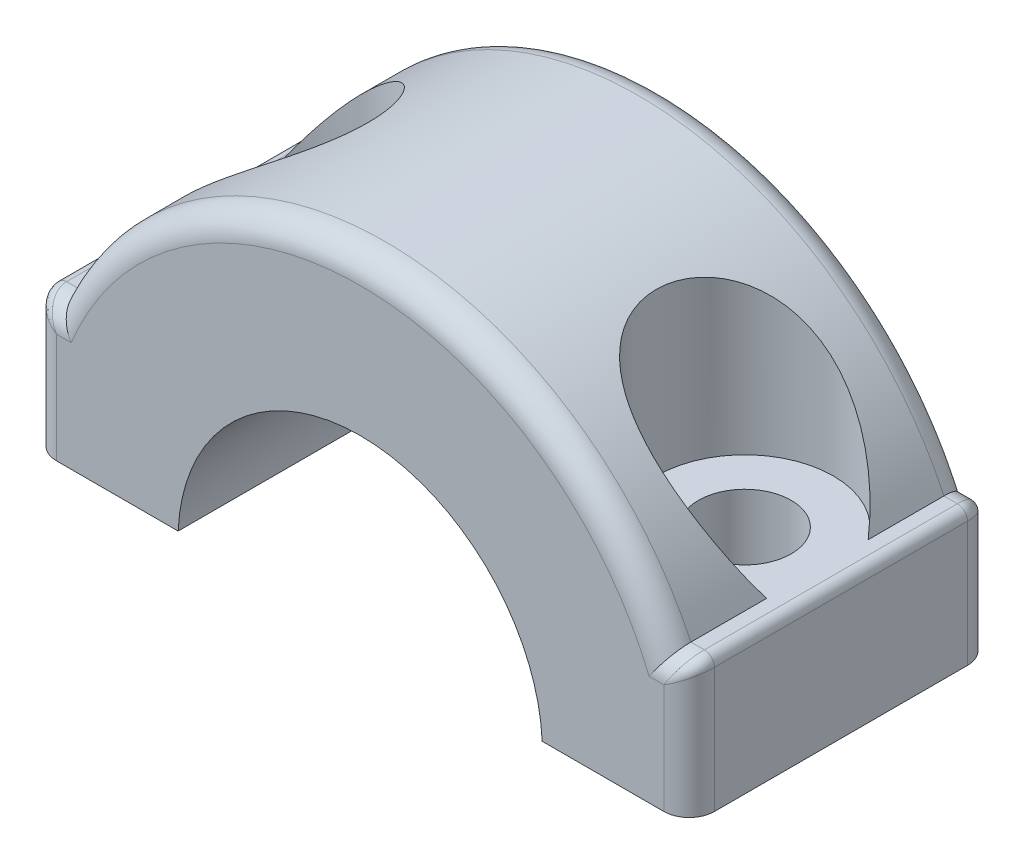
SolidWorks part; units mm, degrees
ref_plane "Front Plane" through (0, 0, 0) normal (0, 0, 1) x (1, 0, 0)
ref_plane "Top Plane" through (0, 0, 0) normal (0, 1, 0) x (1, 0, 0)
ref_plane "Right Plane" through (0, 0, 0) normal (1, 0, 0) x (0, 0, -1)
sketch "Sketch3" plane through (0, 0, 0) normal (0, 1, 0) x (1, 0, 0)
  line L0 (8.7, -18) -> (1.5, -18) construction
  line L1 (0, 0) -> (39, 0) construction
  line L2 (0, 0) -> (0, -18) construction
  line L3 (0, -18) -> (39, -18) construction
  line L4 (39, 0) -> (39, -18) construction
  line L6 (39, -1.5) -> (39, -16.5) construction
sketch "Sketch4" plane through (0, 0, 0) normal (0, 0, 1) x (1, 0, 0)
  line L0 (30.2884, 0.5) -> (39, 0.5)
  line L1 (0, 8.5) -> (1.3961, 8.5)
  line L2 (0, 8.5) -> (0, 0.5)
  line L3 (0, 0.5) -> (8.7116, 0.5)
  line L4 (39, 8.5) -> (39, 0.5)
  line L5 (37.6039, 8.5) -> (39, 8.5)
  arc A0 (30.2884, 0.5) -> (8.7116, 0.5) centre (19.5, 0) ccw
  arc A1 (37.6039, 8.5) -> (1.3961, 8.5) centre (19.5, 0) ccw
  arc A2 (8.7, 0) -> (30.3, 0) centre (19.5, 0) ccw construction
  dimension "D2" = 20
  dimension "D1" = 0.5
  dimension "D3" = 8
extrude "Boss-Extrude1" add sketch "Sketch4" along normal up to vertex (18 mm away) up to point (0, 0, 18)
ref_plane "Plane1" through (0, 8.5, 0) normal (0, 1, 0) x (1, 0, 0)
sketch "Sketch5" plane through (0, 8.5, 0) normal (0, 1, 0) x (1, 0, 0)
  circle A0 centre (33.3, -9) radius 2.75
  circle A1 centre (5.7, -9) radius 2.75
  circle A2 centre (5.7, -9) radius 2.1 construction
  circle A3 centre (33.3, -9) radius 2.1 construction
  dimension "D1" = 5.5
extrude "Cut-Extrude1" cut sketch "Sketch5" along direction (0, 1, 0) on the side against the normal up to surface (8 mm away) up to face at (4.3558, 0.5, 9)
sketch "Sketch6" plane through (0, 8.5, 0) normal (0, 1, 0) x (1, 0, 0)
  circle A0 centre (5.7, -9) radius 5.25
  circle A1 centre (33.3, -9) radius 5.25
  circle A2 centre (5.7, -9) radius 2.1 construction
  dimension "D1" = 10.5
extrude "Cut-Extrude2" cut sketch "Sketch6" along normal through all
fillet "Fillet1" radius 1.5 10 edges at (39, 4.5, 18) (38.3019, 8.5, 18) (38.3019, 8.5, 0) (39, 4.5, 0) (19.5, 20, 0) (0, 4.5, 0) (0.6981, 8.5, 0) (19.5, 20, 18) (0.6981, 8.5, 18) (0, 4.5, 18)
fillet "Fillet2" radius 0.6 6 edges at (0.4393, 8.0607, 17.5607) (0.4393, 8.0607, 0.4393) (38.5607, 8.0607, 17.5607) (38.5607, 8.0607, 0.4393) (0, 8.5, 9) (39, 8.5, 9)
